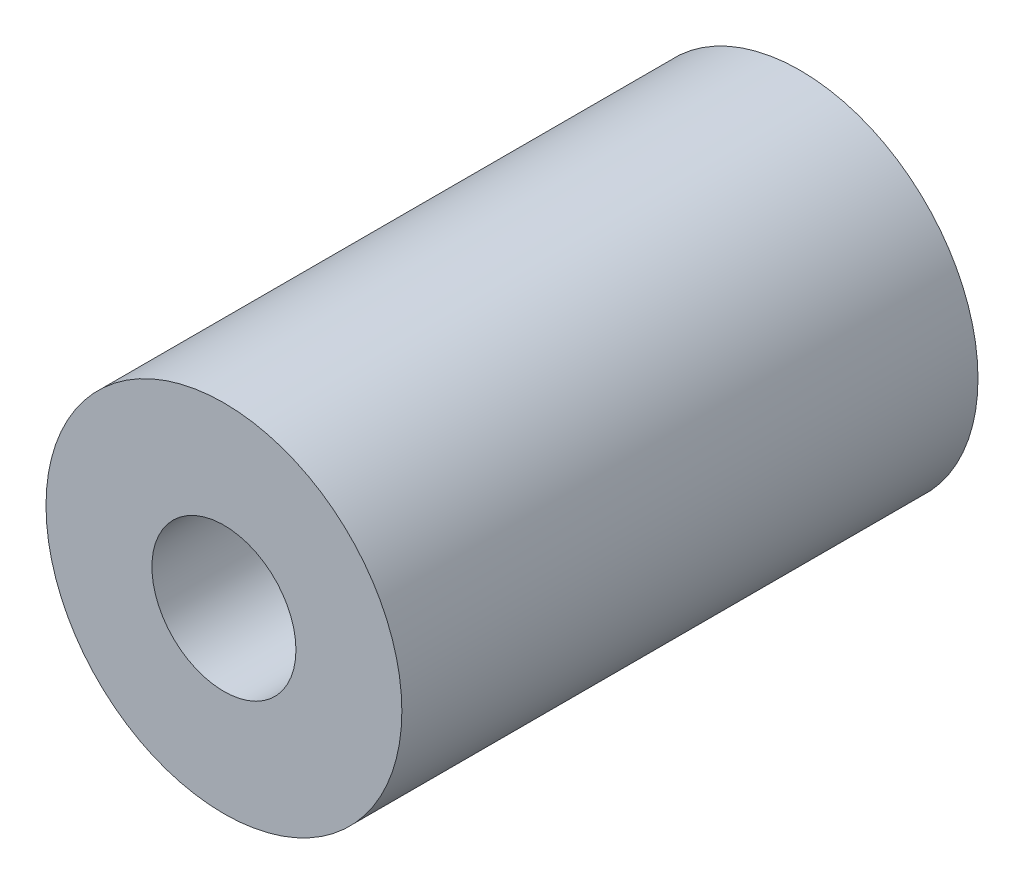
SolidWorks part; units mm, degrees
ref_plane "Front Plane" through (0, 0, 0) normal (0, 0, 1) x (1, 0, 0)
ref_plane "Top Plane" through (0, 0, 0) normal (0, 1, 0) x (1, 0, 0)
ref_plane "Right Plane" through (0, 0, 0) normal (1, 0, 0) x (0, 0, -1)
sketch "Sketch1" plane through (0, 0, 0) normal (0, 1, 0) x (1, 0, 0)
  line L0 (2.125, -3.75) -> (5.25, -3.75)
  line L1 (5.25, -3.75) -> (5.25, 0)
  line L2 (5.25, 0) -> (2.125, 0)
  line L3 (2.125, 0) -> (2.125, -3.75)
  line L4 (0, 0) -> (0, -3.75) construction
  dimension "D1" = 2.125
  dimension "D2" = 5.25
  dimension "D3" = 3.75
revolve "Revolve1" add sketch "Sketch1" angle 360 about L4 reverse direction yes
sketch "Sketch2" plane through (0, 0, 3.75) normal (0, 0, 1) x (1, 0, 0)
  circle A0 centre (0, 0) radius 2.125
  circle A1 centre (0, 0) radius 5.25
  dimension "D1" = 4.25
  dimension "D2" = 10.5
extrude "Boss-Extrude1" add sketch "Sketch2" along normal blind 13.25
